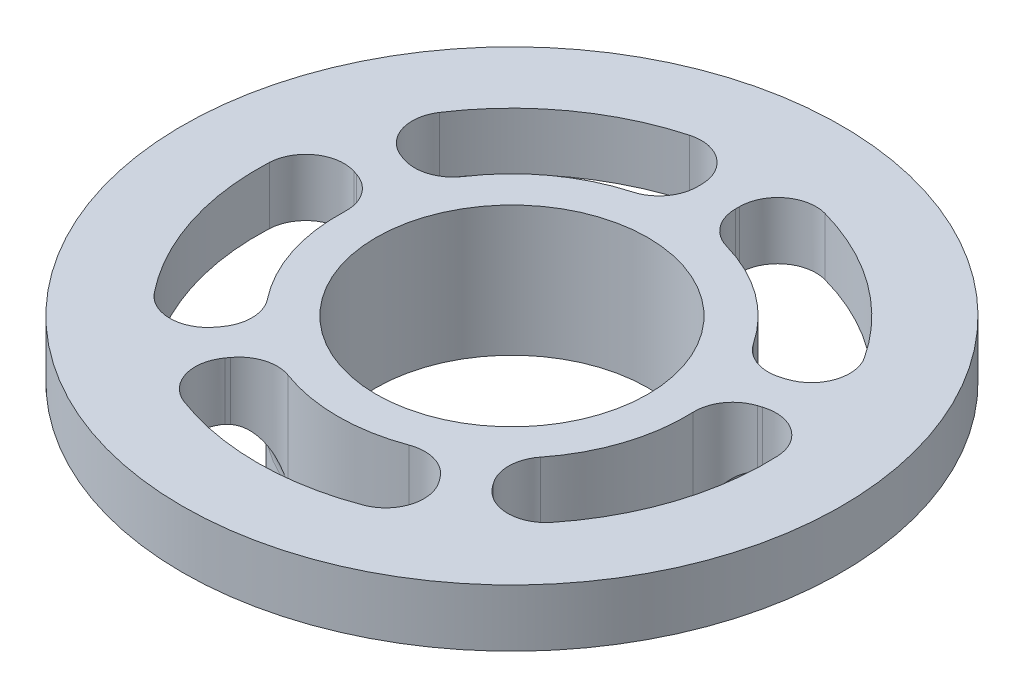
SolidWorks part; units mm, degrees
ref_plane "Alzado" through (0, 0, 0) normal (0, 0, 1) x (1, 0, 0)
ref_plane "Planta" through (0, 0, 0) normal (0, 1, 0) x (1, 0, 0)
ref_plane "Vista lateral" through (0, 0, 0) normal (1, 0, 0) x (0, 0, -1)
sketch "Croquis1" plane through (0, 0, 0) normal (0, 1, 0) x (1, 0, 0)
  line L0 (0, 13.3) -> (0, 0) construction
  line L12 (-1, 13.2624) -> (-1, 9.0449)
  line L15 (1, 13.2624) -> (1, 9.0449)
  line L16 (16.3819, 5.3228) -> (0, 0) construction
  line L17 (12.3042, 5.0493) -> (8.2932, 3.7461)
  line L18 (12.9223, 3.1472) -> (8.9112, 1.844)
  line L19 (10.1246, -13.9353) -> (0, 0) construction
  line L20 (8.6044, -10.1417) -> (6.1255, -6.7297)
  line L21 (6.9864, -11.3173) -> (4.5074, -7.9053)
  line L22 (-10.1246, -13.9353) -> (0, 0) construction
  line L23 (-6.9864, -11.3173) -> (-4.5074, -7.9053)
  line L24 (-8.6044, -10.1417) -> (-6.1255, -6.7297)
  line L25 (-16.3819, 5.3228) -> (0, 0) construction
  line L26 (-12.9223, 3.1472) -> (-8.9112, 1.844)
  line L27 (-12.3042, 5.0493) -> (-8.2932, 3.7461)
  circle A0 centre (0, 0) radius 17.225
  arc A14 (-12.9223, 3.1472) -> (-8.6044, -10.1417) centre (0, 0) ccw
  arc A15 (-8.9112, 1.844) -> (-6.1255, -6.7297) centre (0, 0) ccw
  circle A16 centre (0, 0) radius 7.1
  arc A17 (-1, 9.0449) -> (-8.2932, 3.7461) centre (0, 0) ccw
  arc A18 (-1, 13.2624) -> (-12.3042, 5.0493) centre (0, 0) ccw
  arc A19 (12.3042, 5.0493) -> (1, 13.2624) centre (0, 0) ccw
  arc A20 (8.2932, 3.7461) -> (1, 9.0449) centre (0, 0) ccw
  arc A21 (6.1255, -6.7297) -> (8.9112, 1.844) centre (0, 0) ccw
  arc A22 (-4.5074, -7.9053) -> (4.5074, -7.9053) centre (0, 0) ccw
  arc A23 (-6.9864, -11.3173) -> (6.9864, -11.3173) centre (0, 0) ccw
  arc A24 (8.6044, -10.1417) -> (12.9223, 3.1472) centre (0, 0) ccw
  point P31 (0, 0)
  point P33 (0, 0)
  point P35 (0, 0)
  dimension "D1" = 26.6
  dimension "D2" = 34.45
  dimension "D3" = 3.925
  dimension "D4" = 14.2
  dimension "D5" = 2
  dimension "D11" = 2
  dimension "D6" = 1
  dimension "D8" = 5
  dimension "D9" = 1
  dimension "D10" = 1
  dimension "D7" = 1
  dimension "D12" = 13.3
extrude "Saliente-Extruir1" add sketch "Croquis1" along normal blind 3
sketch "Croquis2" plane through (0, 0, 0) normal (0, -1, 0) x (1, 0, 0)
  line L0 (0, 17.225) -> (0, 0) construction
  line L1 (5.3228, 16.3819) -> (0, 0) construction
  line L2 (10.1246, 13.9353) -> (0, 0) construction
  line L3 (13.9353, 10.1246) -> (0, 0) construction
  line L4 (16.3819, 5.3228) -> (0, 0) construction
  line L5 (17.225, 0) -> (0, 0) construction
  line L6 (16.3819, -5.3228) -> (0, 0) construction
  line L7 (13.9353, -10.1246) -> (0, 0) construction
  line L8 (10.1246, -13.9353) -> (0, 0) construction
  line L9 (5.3228, -16.3819) -> (0, 0) construction
  line L10 (0, -17.225) -> (0, 0) construction
  line L11 (-5.3228, -16.3819) -> (0, 0) construction
  line L12 (-10.1246, -13.9353) -> (0, 0) construction
  line L13 (-13.9353, -10.1246) -> (0, 0) construction
  line L14 (-16.3819, -5.3228) -> (0, 0) construction
  line L15 (-17.225, 0) -> (0, 0) construction
  line L16 (-16.3819, 5.3228) -> (0, 0) construction
  line L17 (-13.9353, 10.1246) -> (0, 0) construction
  line L18 (-10.1246, 13.9353) -> (0, 0) construction
  line L19 (-5.3228, 16.3819) -> (0, 0) construction
  circle A0 centre (0, 0) radius 17.225 construction
  circle A1 centre (0, 15.275) radius 1.25
  circle A3 centre (4.7202, 14.5274) radius 1.25
  circle A4 centre (8.9784, 12.3577) radius 1.25
  circle A5 centre (12.3577, 8.9784) radius 1.25
  circle A6 centre (14.5274, 4.7202) radius 1.25
  circle A7 centre (15.275, 0) radius 1.25
  circle A8 centre (14.5274, -4.7202) radius 1.25
  circle A9 centre (12.3577, -8.9784) radius 1.25
  circle A10 centre (8.9784, -12.3577) radius 1.25
  circle A11 centre (4.7202, -14.5274) radius 1.25
  circle A12 centre (0, -15.275) radius 1.25
  circle A13 centre (-4.7202, -14.5274) radius 1.25
  circle A14 centre (-8.9784, -12.3577) radius 1.25
  circle A15 centre (-12.3577, -8.9784) radius 1.25
  circle A16 centre (-14.5274, -4.7202) radius 1.25
  circle A17 centre (-15.275, 0) radius 1.25
  circle A18 centre (-14.5274, 4.7202) radius 1.25
  circle A19 centre (-12.3577, 8.9784) radius 1.25
  circle A20 centre (-8.9784, 12.3577) radius 1.25
  circle A21 centre (-4.7202, 14.5274) radius 1.25
  point P70 (0, 0)
  dimension "D1" = 2.5
  dimension "D2" = 1.95
  dimension "D3" = 20
extrude "Cortar-Extruir1" cut sketch "Croquis2" against normal blind 1.2
sketch "Croquis5" plane through (0, 0, 0) normal (0, -1, 0) x (1, 0, 0)
  circle A0 centre (0, 0) radius 7.1
  circle A1 centre (0, 0) radius 9.1
  dimension "D1" = 14.2
  dimension "D2" = 2
extrude "Saliente-Extruir2" add sketch "Croquis5" along normal blind 3.8
fillet "Redondeo11" radius 2 10 edges at (8.2932, 1.5, -3.7461) (1, 1.5, -9.0449) (-8.2932, 1.5, -3.7461) (-8.9112, 1.5, -1.844) (-1, 1.5, -9.0449) (-6.1255, 1.5, 6.7297) (4.5074, 1.5, 7.9053) (8.9112, 1.5, -1.844) (6.1255, 1.5, 6.7297) (-4.5074, 1.5, 7.9053)
fillet "Redondeo12" radius 2 5 edges at (-8.6546, 0, -2.8121) (-5.3488, 0, 7.3621) (0, 0, -9.1) (8.6546, 0, -2.8121) (5.3488, 0, 7.3621)
fillet "Redondeo13" radius 2 10 edges at (8.6044, 1.5, 10.1417) (6.9864, 1.5, 11.3173) (12.3042, 1.5, -5.0493) (12.9223, 1.5, -3.1472) (-6.9864, 1.5, 11.3173) (-8.6044, 1.5, 10.1417) (-1, 1.5, -13.2624) (-12.3042, 1.5, -5.0493) (1, 1.5, -13.2624) (-12.9223, 1.5, -3.1472)
